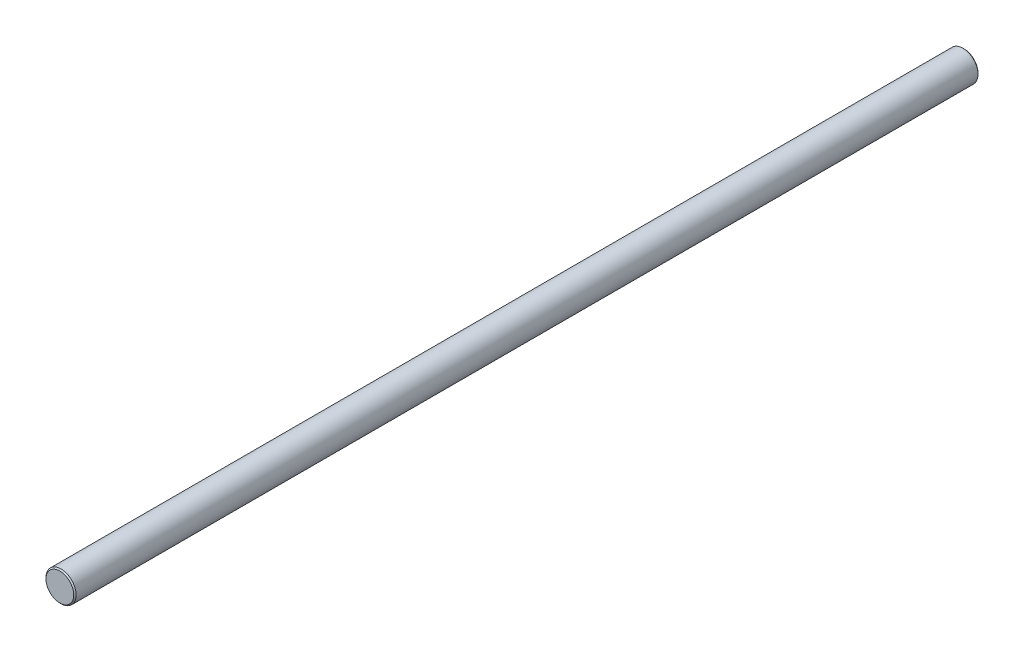
SolidWorks part; units mm, degrees
material "Сталь 45 ГОСТ 1050-88"
ref_plane "Спереди" through (0, 0, 0) normal (0, 0, 1) x (1, 0, 0)
ref_plane "Сверху" through (0, 0, 0) normal (0, 1, 0) x (1, 0, 0)
ref_plane "Справа" through (0, 0, 0) normal (1, 0, 0) x (0, 0, -1)
ref_axis "ОсьX" through (-88.99, 0, 0) along (1, 0, 0)
ref_axis "ОсьZ" through (0, 55, 0) along (0, -1, 0)
ref_axis "ОсьY" through (0, 0, -88.99) along (0, 0, 1)
sketch "Эскиз1" plane through (0, 0, 0) normal (0, 0, 1) x (1, 0, 0)
  circle A0 centre (0, 0) radius 12.5
  dimension "D1" = 25
extrude "Бобышка-Вытянуть1" add sketch "Эскиз1" along normal mid plane 750
chamfer "Фаска1" distance 1 angle 45 2 edges at (12.5, 0, -375) (12.5, 0, 375)
